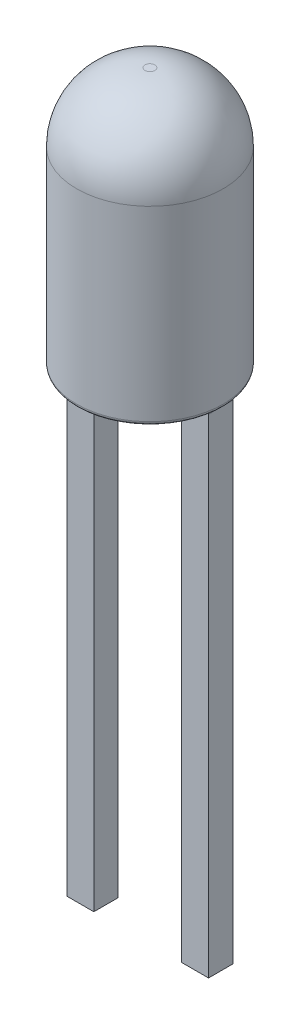
SolidWorks part; units mm, degrees
ref_plane "Front Plane" through (0, 0, 0) normal (0, 0, 1) x (1, 0, 0)
ref_plane "Top Plane" through (0, 0, 0) normal (0, 1, 0) x (1, 0, 0)
ref_plane "Right Plane" through (0, 0, 0) normal (1, 0, 0) x (0, 0, -1)
sketch "Sketch2" plane through (0, 0, 0) normal (0, 1, 0) x (1, 0, 0)
  circle A0 centre (0, 0) radius 1.5
extrude "Boss-Extrude1" add sketch "Sketch2" along normal blind 5.3
fillet "Fillet1" radius 1.4 1 edges at (0, 5.3, 1.5)
sketch "Sketch3" plane through (0, 0, 0) normal (0, 0, 1) x (1, 0, 0)
  line L0 (0, 0) -> (0, 2.6) construction
  line L1 (-1.45, 2.6) -> (1.45, 2.6) construction
  line L2 (-1.45, 2.6) -> (-1.45, 0)
  line L3 (-1.5, 0) -> (1.5, 0) construction
  line L4 (-1.45, 0) -> (-0.9, 0)
  line L5 (-0.9, 0) -> (-0.9, 0.6)
  line L6 (-0.9, 0.6) -> (-0.6241, 0.6)
  line L7 (-0.6241, 0.6) -> (-0.6241, 0.825)
  line L8 (-0.6241, 0.825) -> (-1.2254, 2.6)
  line L9 (-1.2254, 2.6) -> (-1.45, 2.6)
  line L10 (1.45, 2.6) -> (-0.8725, 2.6)
  line L11 (-0.8725, 2.6) -> (0.4967, 0.6)
  line L12 (0.4967, 0.6) -> (0.9, 0.6)
  line L13 (0.9, 0.6) -> (0.9, 0)
  line L14 (0.9, 0) -> (1.45, 0)
  line L15 (1.45, 0) -> (1.45, 2.6)
  line L16 (-0.6241, 0.6) -> (0.4967, 0.6) construction
  line L17 (-0.0637, 0.6) -> (-0.0637, 0) construction
  point P6 (0, 2.6)
extrude "Boss-Extrude2" add sketch "Sketch3" along normal blind 0.25 and the other way blind 0.25 separate body
sketch "Sketch4" plane through (0, 0, 0) normal (0, -1, 0) x (-1, 0, 0)
  line L1 (1.45, -0.25) -> (0.9, -0.25)
  line L2 (1.45, -0.25) -> (1.45, 0.25)
  line L3 (1.45, 0.25) -> (0.9, 0.25)
  line L4 (0.9, -0.25) -> (0.9, 0.25)
  line L5 (-0.9, -0.25) -> (-1.45, -0.25)
  line L6 (-0.9, -0.25) -> (-0.9, 0.25)
  line L7 (-0.9, 0.25) -> (-1.45, 0.25)
  line L8 (-1.45, -0.25) -> (-1.45, 0.25)
extrude "Boss-Extrude3" add sketch "Sketch4" along normal blind 10 separate body
sketch "Sketch5" plane through (0, 0, 0) normal (1, 0, 0) x (0, 0, -1)
  line L0 (0, 2.6) -> (0, 2.3)
  line L1 (0, 2.3) -> (-0.6, 2.6)
  line L2 (-0.6, 2.6) -> (0, 2.6)
  line L3 (0.25, 2.6) -> (-0.25, 2.6) construction
  dimension "D1" = 0.3
  dimension "D2" = 0.6
revolve "Cut-Revolve1" cut sketch "Sketch5" angle 360 about L0
revolve "Revolve1" add sketch "Sketch5<3>" angle 360 about L0
sketch "Sketch5<3>" plane through (0, 0, 0) normal (1, 0, 0) x (0, 0, -1) same geometry as "Sketch5"
fillet "Fillet2" radius 0.05 1 edges at (0, 2.6, 0.6)
fillet "Fillet3" radius 0.08 1 edges at (0, 0, 1.5)
